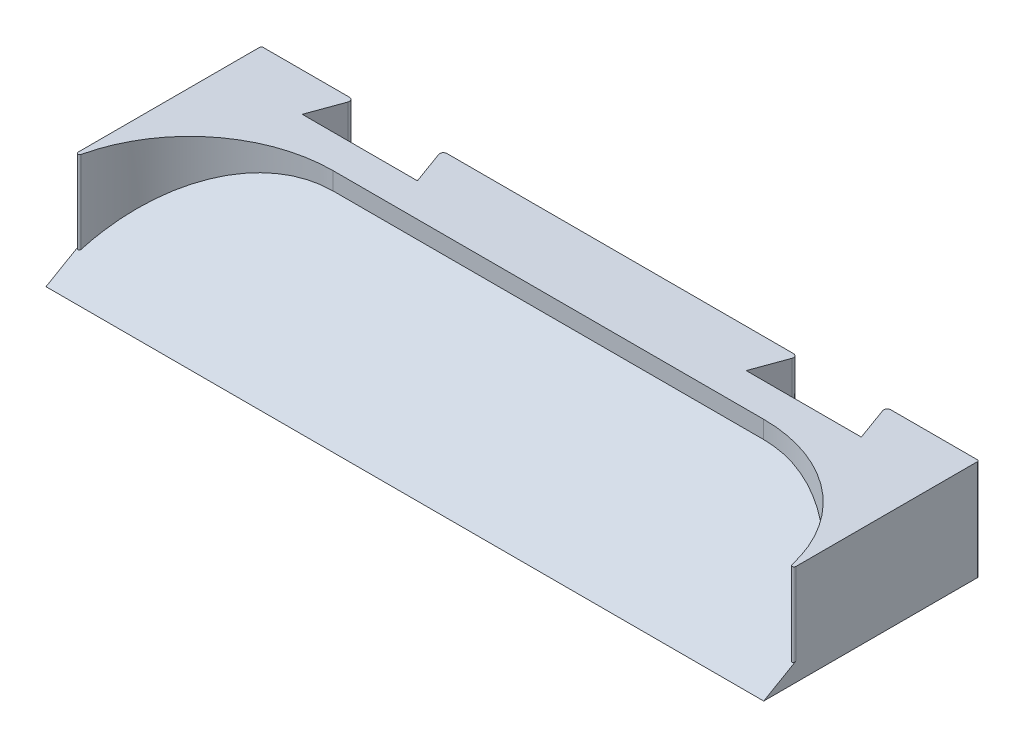
SolidWorks part; units mm, degrees
ref_plane "前视基准面" through (0, 0, 0) normal (0, 0, 1) x (1, 0, 0)
ref_plane "上视基准面" through (0, 0, 0) normal (0, 1, 0) x (1, 0, 0)
ref_plane "右视基准面" through (0, 0, 0) normal (1, 0, 0) x (0, 0, -1)
other "Configuration Table"
sketch "草图1" plane through (0, 0, 0) normal (0, 1, 0) x (1, 0, 0)
  line L1 (0, 0) -> (200, 0)
  line L2 (0, 0) -> (0, -60)
  line L3 (0, -60) -> (200, -60)
  line L4 (200, 0) -> (200, -60)
  dimension "D1" = 60
  dimension "D2" = 200
extrude "凸台-拉伸1" add sketch "草图1" along normal blind 28
sketch "草图2" plane through (0, 0, 0) normal (1, 0, 0) x (0, 0, -1)
  line L0 (-60, 0) -> (-20, 23.094)
  line L1 (-60, 0) -> (0, 0) construction
  line L2 (-20, 23.094) -> (-20, 28)
  line L3 (-60, 28) -> (0, 28) construction
  line L4 (-20, 28) -> (-60, 28)
  line L5 (-60, 28) -> (-60, 0)
  dimension "D1" = 30
  dimension "D2" = 40
extrude "切除-拉伸1" cut sketch "草图2" along normal through all
sketch "草图3" plane through (0, 0, 0) normal (0, 1, 0) x (1, 0, 0)
  line L8 (0, -60) -> (0, -20)
  line L9 (0, -20) -> (40, -20)
  line L10 (200, -20) -> (0, -20) construction
  line L11 (100, 0) -> (100, -70) construction
  line L12 (200, 0) -> (0, 0) construction
  line L13 (200, -20) -> (160, -20)
  line L14 (200, -60) -> (200, -20)
  arc A2 (0, -60) -> (40, -20) centre (40, -60) cw
  arc A3 (200, -60) -> (160, -20) centre (160, -60) ccw
  dimension "D1" = 40
extrude "凸台-拉伸2" add sketch "草图3" along normal up to surface (28 mm away) up to face at (100, 28, 10)
fillet "圆角1" radius 0.5 4 edges at (200, 14, 60) (0, 14, 60) (0, 14, 0) (200, 14, 0)
sketch "草图4" plane through (0, 0, 0) normal (0, 1, 0) x (1, 0, 0)
  line L0 (26, 0) -> (22.1055, -10.7)
  line L1 (199.5, 0) -> (0.5, 0) construction
  line L2 (22.1055, -10.7) -> (54.1945, -10.7)
  line L3 (54.1945, -10.7) -> (50.3, 0)
  line L5 (100, 0) -> (100, -25.2891) construction
  line L6 (26, 0) -> (50.3, 0)
  line L7 (145.8055, -10.7) -> (149.7, 0)
  line L8 (174, 0) -> (177.8945, -10.7)
  line L9 (177.8945, -10.7) -> (145.8055, -10.7)
  line L10 (174, 0) -> (149.7, 0)
  arc A0 (0.5, 0) -> (0, -0.5) centre (0.5, -0.5) ccw construction
  dimension "D1" = 70
  dimension "D2" = 26
  dimension "D3" = 70
  dimension "D4" = 24.3
  dimension "D5" = 10.2
extrude "切除-拉伸2" cut sketch "草图4" along normal through all from offset 12
sketch "草图5" plane through (0, 0, 0) normal (0, 1, 0) x (1, 0, 0)
  line L5 (100, 0) -> (100, -60) construction
  line L6 (149.7, 0) -> (50.3, 0) construction
  line L7 (0, -60) -> (200, -60) construction
  line L12 (0, -0.5) -> (0, -51.0557) construction
  line L13 (12, -18) -> (72, -18)
  line L14 (12, -18) -> (12, -30)
  line L15 (12, -30) -> (72, -30)
  line L16 (72, -18) -> (72, -30)
  line L18 (128, -18) -> (128, -30)
  line L19 (188, -30) -> (128, -30)
  line L20 (188, -18) -> (128, -18)
  line L21 (188, -18) -> (188, -30)
  point P15 (13.6075, 13.8719)
  dimension "D1" = 12
  dimension "D2" = 12
  dimension "D3" = 60
  dimension "D4" = 30
extrude "切除-拉伸3" cut sketch "草图5" against normal through all from offset 10
sketch "草图6" plane through (0, 0, 0) normal (0, 0, 1) x (1, 0, 0)
  line L3 (100, 28) -> (100, 0) construction
  line L6 (60, 10) -> (72, 10)
  line L10 (60, 10) -> (60, 5)
  line L11 (60, 5) -> (72, 5)
  line L12 (72, 10) -> (72, 5)
  line L19 (160, 28) -> (40, 28) construction
  line L20 (0, 0) -> (200, 0) construction
  line L21 (128, 10) -> (128, 5)
  line L22 (140, 5) -> (128, 5)
  line L23 (140, 10) -> (140, 5)
  line L24 (140, 10) -> (128, 10)
  dimension "D1" = 5
  dimension "D2" = 5
  dimension "D3" = 60
  dimension "D4" = 12
extrude "切除-拉伸4" cut sketch "草图6" along normal up to surface (30 mm away) up to face at (158, 5, 30)
fillet "圆角2" radius 1 14 edges at (134, 5, 18) (66, 5, 18) (66, 5, 0) (60, 7.5, 0) (72, 7.5, 0) (66, 10, 0) (140, 7.5, 0) (134, 5, 0) (134, 10, 0) (128, 7.5, 0) (174, 20, 0) (149.7, 20, 0) (50.3, 20, 0) (26, 20, 0)
